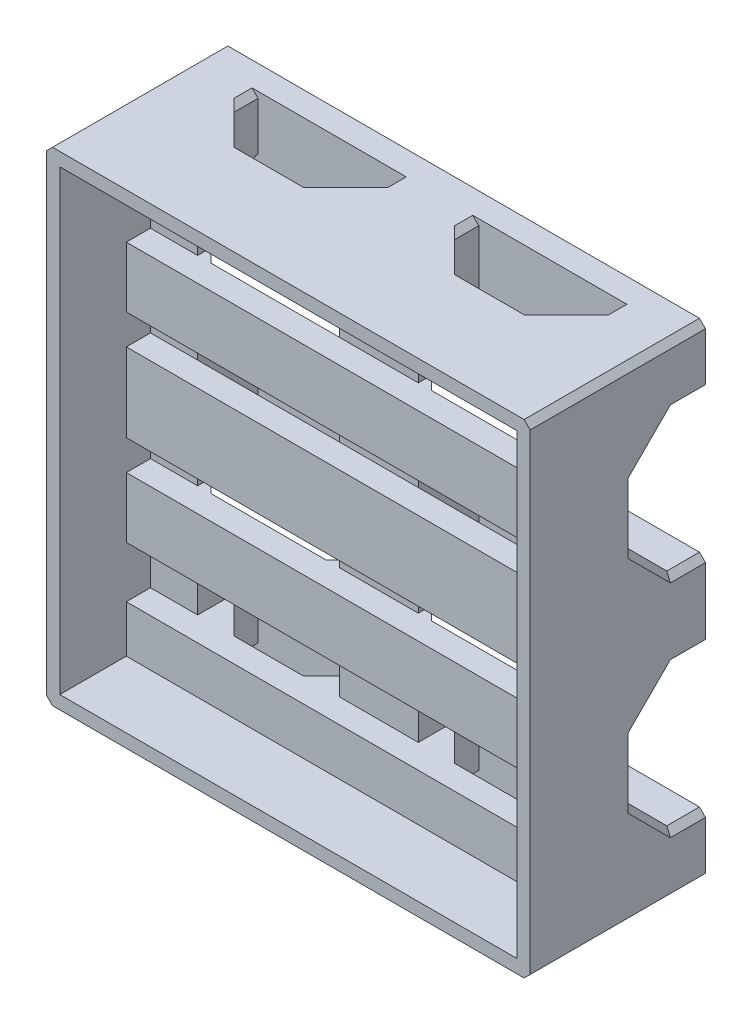
SolidWorks part; units mm, degrees
ref_plane "Alzado" through (0, 0, 0) normal (1, 0, 0) x (0, 1, 0)
ref_plane "Planta" through (0, 0, 0) normal (0, 0, 1) x (0, 1, 0)
ref_plane "Vista lateral" through (0, 0, 0) normal (0, 1, 0) x (-1, 0, 0)
sketch "Croquis1" plane through (0, 0, 0) normal (0, 0, 1) x (0, 1, 0)
  line L0 (0, 0) -> (40, 0) construction
  line L5 (0, 0) -> (0, 40) construction
  line L7 (-30, 40) -> (-40, -40) construction
  line L8 (-6.5, 40) -> (6.5, 40)
  line L9 (-6.5, 40) -> (-6.5, -40)
  line L10 (-6.5, -40) -> (6.5, -40)
  line L11 (6.5, 40) -> (6.5, -40)
  line L12 (-6.5, 40) -> (6.5, -40) construction
  line L13 (-6.5, -40) -> (6.5, 40) construction
  line L14 (30, -40) -> (40, -40)
  line L15 (30, -40) -> (30, 40)
  line L16 (30, 40) -> (40, 40)
  line L17 (40, -40) -> (40, 40)
  line L18 (30, -40) -> (40, 40) construction
  line L19 (30, 40) -> (40, -40) construction
  line L20 (-30, -40) -> (-40, 40) construction
  line L21 (-40, -40) -> (-40, 40)
  line L22 (-30, 40) -> (-40, 40)
  line L23 (-30, -40) -> (-30, 40)
  line L24 (-30, -40) -> (-40, -40)
  point P9 (35, 0)
  point P18 (-35, 0)
  dimension "D1" = 40
  dimension "D2" = 40
  dimension "D3" = 13
  dimension "D4" = 10
extrude "Saliente-Extruir1" add sketch "Croquis1" along normal blind 4
sketch "Croquis2" plane through (0, 0, 4) normal (0, 0, 1) x (1, 0, 0)
  line L0 (40, 0) -> (0, 0) construction
  line L1 (40, 30) -> (40, 40) construction
  line L2 (40, -6.5) -> (40, 6.5) construction
  line L3 (0, 0) -> (0, 35) construction
  line L5 (-40, -6.5) -> (40, -6.5) construction
  line L6 (-6.5, 6.5) -> (6.5, 6.5)
  line L7 (-6.5, 6.5) -> (-6.5, -6.5)
  line L8 (-6.5, -6.5) -> (6.5, -6.5)
  line L9 (6.5, 6.5) -> (6.5, -6.5)
  line L10 (-6.5, 6.5) -> (6.5, -6.5) construction
  line L11 (-6.5, -6.5) -> (6.5, 6.5) construction
  line L12 (-40, 6.5) -> (-40, -6.5) construction
  line L13 (-30, -6.5) -> (-40, -6.5)
  line L14 (-30, -6.5) -> (-30, 6.5)
  line L15 (-30, 6.5) -> (-40, 6.5)
  line L16 (-40, -6.5) -> (-40, 6.5)
  line L17 (-30, -6.5) -> (-40, 6.5) construction
  line L18 (-30, 6.5) -> (-40, -6.5) construction
  line L19 (30, 6.5) -> (40, -6.5) construction
  line L20 (30, -6.5) -> (40, 6.5) construction
  line L21 (40, -6.5) -> (40, 6.5)
  line L22 (30, 6.5) -> (40, 6.5)
  line L23 (30, -6.5) -> (30, 6.5)
  line L24 (30, -6.5) -> (40, -6.5)
  line L25 (-40, 30) -> (40, 30) construction
  line L26 (-6.5, 40) -> (6.5, 40)
  line L27 (-6.5, 40) -> (-6.5, 30)
  line L28 (-6.5, 30) -> (6.5, 30)
  line L29 (6.5, 40) -> (6.5, 30)
  line L30 (-6.5, 40) -> (6.5, 30) construction
  line L31 (-6.5, 30) -> (6.5, 40) construction
  line L32 (40, 30) -> (30, 40) construction
  line L33 (-40, 40) -> (-30, 40)
  line L34 (-40, 40) -> (-40, 30)
  line L35 (-40, 30) -> (-30, 30)
  line L36 (-30, 40) -> (-30, 30)
  line L37 (-40, 40) -> (-30, 30) construction
  line L38 (-40, 30) -> (-30, 40) construction
  line L39 (40, 40) -> (30, 30) construction
  line L40 (30, 40) -> (30, 30)
  line L41 (40, 30) -> (30, 30)
  line L42 (40, 40) -> (40, 30)
  line L43 (40, 40) -> (30, 40)
  line L44 (40, -40) -> (30, -30) construction
  line L45 (-40, -30) -> (-30, -40) construction
  line L46 (-40, -40) -> (-30, -30) construction
  line L47 (40, -30) -> (30, -40) construction
  line L48 (-6.5, -30) -> (6.5, -40) construction
  line L49 (-6.5, -40) -> (6.5, -30) construction
  line L50 (40, -40) -> (30, -40)
  line L51 (40, -40) -> (40, -30)
  line L52 (40, -30) -> (30, -30)
  line L53 (30, -40) -> (30, -30)
  line L54 (-30, -40) -> (-30, -30)
  line L55 (-40, -30) -> (-30, -30)
  line L56 (-40, -40) -> (-40, -30)
  line L57 (-40, -40) -> (-30, -40)
  line L58 (6.5, -40) -> (6.5, -30)
  line L59 (-6.5, -30) -> (6.5, -30)
  line L60 (-6.5, -40) -> (-6.5, -30)
  line L61 (-6.5, -40) -> (6.5, -40)
  point P8 (40, 35)
  point P14 (-35, 0)
  point P25 (35, 0)
  point P33 (-35, 35)
  point P43 (35, 35)
  point P56 (35, -35)
  point P57 (-35, -35)
  point P58 (40, -35)
  dimension "D1" = 13
  dimension "D2" = 10
extrude "Saliente-Extruir2" add sketch "Croquis2" along normal blind 10
sketch "Croquis3" plane through (0, 0, 14) normal (0, 0, 1) x (1, 0, 0)
  line L0 (0, 0) -> (40, 0) construction
  line L1 (40, -6.5) -> (40, 6.5) construction
  line L2 (0, 0) -> (0, 40) construction
  line L3 (6.5, 40) -> (-6.5, 40) construction
  line L4 (-40, 6.5) -> (-40, -6.5) construction
  line L5 (-6.5, -40) -> (6.5, -40)
  line L6 (-6.5, -40) -> (-6.5, 40)
  line L7 (-6.5, 40) -> (6.5, 40)
  line L8 (6.5, -40) -> (6.5, 40)
  line L9 (-6.5, -40) -> (6.5, 40) construction
  line L10 (-6.5, 40) -> (6.5, -40) construction
  line L11 (-40, -40) -> (-30, -40)
  line L12 (-40, -40) -> (-40, 40)
  line L13 (-40, 40) -> (-30, 40)
  line L14 (-30, -40) -> (-30, 40)
  line L15 (-40, -40) -> (-30, 40) construction
  line L16 (-40, 40) -> (-30, -40) construction
  line L17 (-40, -40) -> (-30, -40) construction
  line L18 (40, 40) -> (30, -40) construction
  line L19 (40, -40) -> (30, 40) construction
  line L20 (30, -40) -> (30, 40)
  line L21 (40, 40) -> (30, 40)
  line L22 (40, -40) -> (40, 40)
  line L23 (40, -40) -> (30, -40)
  point P13 (-35, 0)
  point P27 (35, 0)
extrude "Saliente-Extruir3" add sketch "Croquis3" against normal blind 2.2
sketch "Croquis4" plane through (0, 0, 14) normal (0, 0, 1) x (1, 0, 0)
  line L0 (-40, -30) -> (40, -30) construction
  line L1 (40, -30) -> (40, -40) construction
  line L2 (40, -40) -> (-40, -40) construction
  line L3 (-40, -40) -> (-40, -30) construction
  line L4 (-40, 6.5) -> (40, 6.5) construction
  line L5 (40, 6.5) -> (40, -6.5) construction
  line L6 (40, -6.5) -> (-40, -6.5) construction
  line L7 (-40, -6.5) -> (-40, 6.5) construction
  line L8 (-40, 40) -> (40, 40) construction
  line L9 (40, 40) -> (40, 30) construction
  line L10 (40, 30) -> (-40, 30) construction
  line L11 (-40, 30) -> (-40, 40) construction
  line L12 (-40, -30) -> (40, -30)
  line L13 (40, -30) -> (40, -40)
  line L14 (40, -40) -> (-40, -40)
  line L15 (-40, -40) -> (-40, -30)
  line L16 (-40, 6.5) -> (40, 6.5)
  line L17 (40, 6.5) -> (40, -6.5)
  line L18 (40, -6.5) -> (-40, -6.5)
  line L19 (-40, -6.5) -> (-40, 6.5)
  line L20 (-40, 40) -> (40, 40)
  line L21 (40, 40) -> (40, 30)
  line L22 (40, 30) -> (-40, 30)
  line L23 (-40, 30) -> (-40, 40)
  line L24 (0, 0) -> (40, 0) construction
  line L25 (40, -40) -> (40, 40) construction
  line L26 (-40, 21.5) -> (40, 21.5)
  line L27 (-40, 21.5) -> (-40, 11.5)
  line L28 (-40, 11.5) -> (40, 11.5)
  line L29 (40, 21.5) -> (40, 11.5)
  line L30 (-40, 21.5) -> (40, 11.5) construction
  line L31 (-40, 11.5) -> (40, 21.5) construction
  line L32 (-40, -11.5) -> (40, -21.5) construction
  line L33 (-40, -21.5) -> (40, -11.5) construction
  line L34 (40, -21.5) -> (40, -11.5)
  line L35 (-40, -11.5) -> (40, -11.5)
  line L36 (-40, -21.5) -> (-40, -11.5)
  line L37 (-40, -21.5) -> (40, -21.5)
  point P15 (0, 16.5)
  point P27 (0, -16.5)
  dimension "D1" = 5
  dimension "D2" = 10
extrude "Saliente-Extruir4" add sketch "Croquis4" along normal blind 4
sketch "Croquis5" plane through (0, 0, 14) normal (0, 0, 1) x (1, 0, 0)
  line L0 (-37.8, -37.8) -> (-37.8, 37.8)
  line L1 (40, -40) -> (-40, -40)
  line L2 (40, -40) -> (40, 40)
  line L3 (40, 40) -> (-40, 40)
  line L4 (-40, -40) -> (-40, 40)
  line L5 (40, -40) -> (-40, 40) construction
  line L6 (40, 40) -> (-40, -40) construction
  line L7 (37.8, 37.8) -> (-37.8, 37.8)
  line L8 (37.8, -37.8) -> (37.8, 37.8)
  line L9 (37.8, -37.8) -> (-37.8, -37.8)
  point P0 (0, 0)
  dimension "D1" = 2.2
extrude "Saliente-Extruir5" add sketch "Croquis5" along normal blind 15
chamfer "Chaflán2" distance 6.4 angle 45 12 edges at (35, -30, 11.8) (0, 6.5, 11.8) (0, -6.5, 11.8) (-35, -6.5, 11.8) (-35, 30, 11.8) (0, 30, 11.8) (-35, 6.5, 11.8) (-35, -30, 11.8) (0, -30, 11.8) (35, 6.5, 11.8) (35, 30, 11.8) (35, -6.5, 11.8)
chamfer "Chaflán3" distance 6 angle 45 8 edges at (30, -35, 14) (6.5, -35, 14) (-6.5, -35, 14) (-30, -35, 14) (-6.5, 35, 14) (-30, 35, 14) (6.5, 35, 14) (30, 35, 14)
chamfer "Chaflán4" distance 2.2 angle 45 7 edges at (6.5, -16.5, 14) (6.5, 16.5, 14) (30, -16.5, 14) (30, 16.5, 14) (-6.5, -16.5, 14) (-30, -16.5, 14) (-30, 16.5, 14)
sketch "Croquis6" plane through (-40, 0, 0) normal (-1, 0, 0) x (0, -1, 0)
  line L0 (0, 0) -> (0, 29) construction
  line L1 (-40, 29) -> (40, 29) construction
  line L2 (0, 14.5) -> (32.8519, 14.5) construction
  line L4 (-5, 19.5) -> (5, 19.5)
  line L5 (-5, 19.5) -> (-5, 9.5)
  line L6 (-5, 9.5) -> (5, 9.5)
  line L7 (5, 19.5) -> (5, 9.5)
  line L8 (-5, 19.5) -> (5, 9.5) construction
  line L9 (-5, 9.5) -> (5, 19.5) construction
  dimension "D1" = 10
  dimension "D2" = 10
extrude "Cortar-Extruir1" cut sketch "Croquis6" against normal blind 0.4
fillet "Redondeo1" radius 1 4 edges at (-39.8, 5, 19.5) (-39.8, -5, 19.5) (-39.8, -5, 9.5) (-39.8, 5, 9.5)
chamfer "Chaflán1" distance 1 angle 45 44 edges at (40, -30, 2.7) (-30, 30, 4.7) (-30, -6.5, 4.7) (-30, 6.5, 4.7) (6.5, -6.5, 4.7) (6.5, 6.5, 4.7) (-6.5, 6.5, 4.7) (-6.5, 30, 4.7) (-30, 40, 6) (30, 6.5, 4.7) (30, 30, 4.7) (-6.5, 40, 6) (6.5, 40, 6) (30, 40, 6) (-40, 40, 14.5) (-40, 30, 2.7) (-40, 6.5, 2.7) (-40, -6.5, 2.7) (-40, -30, 2.7) (-40, -40, 14.5) (30, -30, 4.7) (30, -40, 6) (-6.5, -40, 6) (-30, -30, 4.7) (-30, -40, 6) (6.5, -30, 4.7) (6.5, -40, 6) (40, 40, 14.5) (40, 30, 2.7) (40, 6.5, 2.7) (40, -6.5, 2.7) (40, -40, 14.5) (40, -26.8, 8.6) (-40, 26.8, 8.6) (-40, 18.25, 11.8) (-40, 9.7, 8.6) (-40, -9.7, 8.6) (-40, -18.25, 11.8) (-40, -26.8, 8.6) (40, 26.8, 8.6) (40, 18.25, 11.8) (40, 9.7, 8.6) (40, -18.25, 11.8) (40, -9.7, 8.6)
